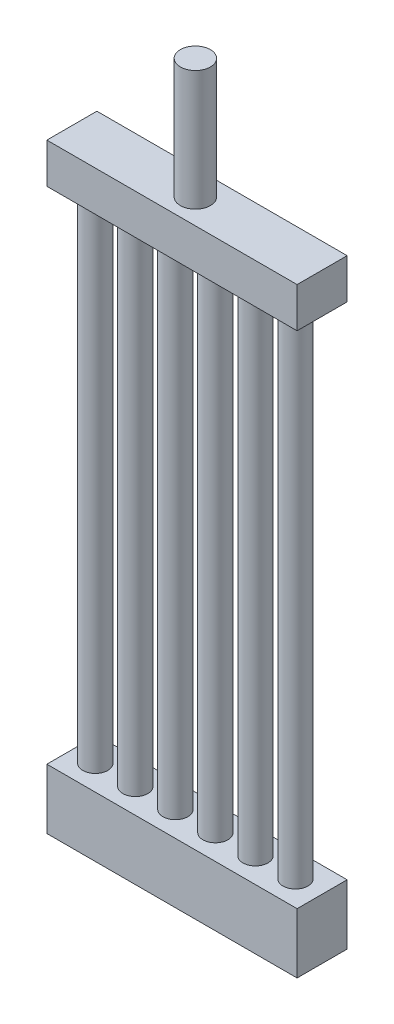
SolidWorks part; units mm, degrees
ref_plane "Front Plane" through (0, 0, 0) normal (0, 0, 1) x (1, 0, 0)
ref_plane "Top Plane" through (0, 0, 0) normal (0, 1, 0) x (1, 0, 0)
ref_plane "Right Plane" through (0, 0, 0) normal (1, 0, 0) x (0, 0, -1)
other "Configuration Table"
sketch "Sketch1" plane through (0, 0, 0) normal (1, 0, 0) x (0, 0, -1)
  line L1 (-34, 190) -> (-39, 190)
  line L2 (-34, 190) -> (-34, 196)
  line L3 (-34, 196) -> (-39, 196)
  line L4 (-39, 190) -> (-39, 196)
  line L5 (-34, 190) -> (-39, 196) construction
  line L6 (-34, 196) -> (-39, 190) construction
extrude "crosshead" add sketch "Sketch1" along normal blind 25 from offset 54 separate body
sketch "Sketch2" plane through (0, 0, 0) normal (0, 1, 0) x (1, 0, 0)
  circle A0 centre (56.34, -36.5) radius 1.25
extrude "sma_spring1" add sketch "Sketch2" along normal blind 50 from offset 196 separate body
sketch "Sketch3" plane through (0, 0, 0) normal (0, 1, 0) x (1, 0, 0)
  circle A0 centre (60.34, -36.5) radius 1.25
extrude "sma_spring2" add sketch "Sketch3" along normal blind 50 from offset 196 separate body
sketch "Sketch4" plane through (0, 0, 0) normal (0, 1, 0) x (1, 0, 0)
  circle A0 centre (64.34, -36.5) radius 1.25
extrude "sma_spring3" add sketch "Sketch4" along normal blind 50 from offset 196 separate body
sketch "Sketch5" plane through (0, 0, 0) normal (0, 1, 0) x (1, 0, 0)
  circle A0 centre (68.34, -36.5) radius 1.25
extrude "sma_spring4" add sketch "Sketch5" along normal blind 50 from offset 196 separate body
sketch "Sketch6" plane through (0, 0, 0) normal (0, 1, 0) x (1, 0, 0)
  circle A0 centre (72.34, -36.5) radius 1.25
extrude "sma_spring5" add sketch "Sketch6" along normal blind 50 from offset 196 separate body
sketch "Sketch7" plane through (0, 0, 0) normal (0, 1, 0) x (1, 0, 0)
  circle A0 centre (76.34, -36.5) radius 1.25
extrude "sma_spring6" add sketch "Sketch7" along normal blind 50 from offset 196 separate body
sketch "Sketch8" plane through (0, 0, 0) normal (1, 0, 0) x (0, 0, -1)
  line L1 (-34, 246) -> (-39, 246)
  line L2 (-34, 246) -> (-34, 250)
  line L3 (-34, 250) -> (-39, 250)
  line L4 (-39, 246) -> (-39, 250)
  line L5 (-34, 246) -> (-39, 250) construction
  line L6 (-34, 250) -> (-39, 246) construction
extrude "anchor_plate" add sketch "Sketch8" along normal blind 25 from offset 54 separate body
sketch "Sketch9" plane through (0, 0, 0) normal (0, 1, 0) x (1, 0, 0)
  circle A0 centre (66.34, -36.5) radius 1.5
extrude "hook" add sketch "Sketch9" along normal blind 12 from offset 250 separate body
